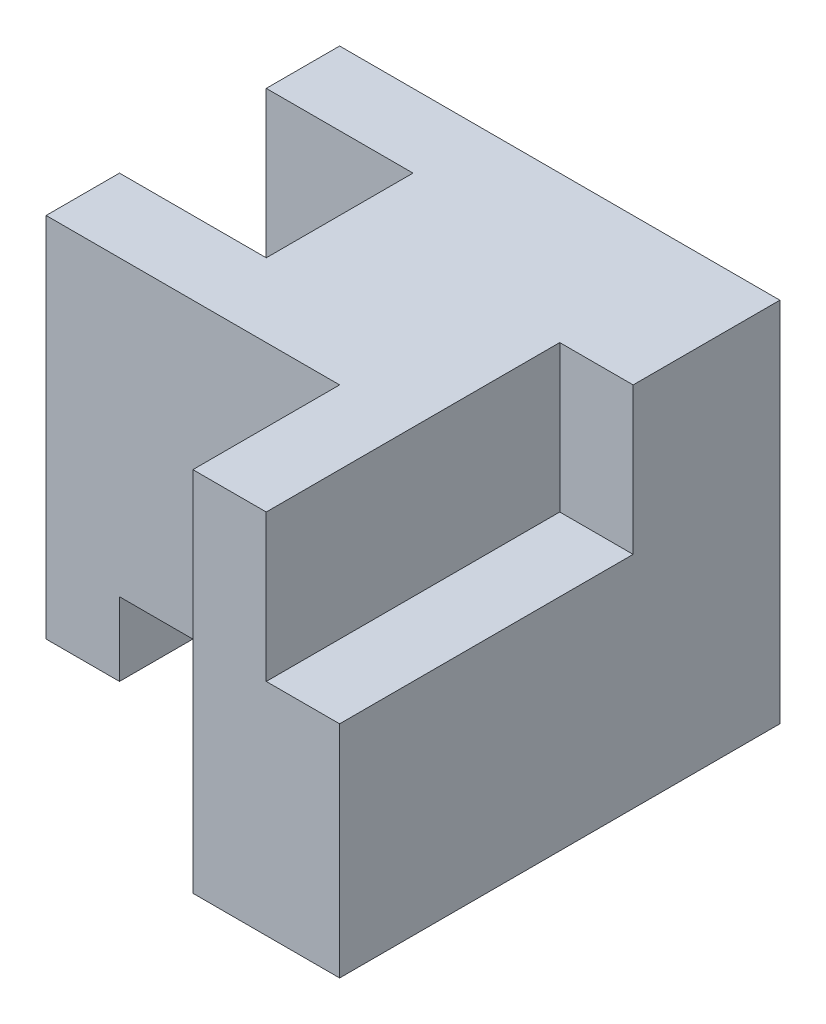
SolidWorks part; units mm, degrees
ref_plane "Front Plane" through (0, 0, 0) normal (0, 0, 1) x (1, 0, 0)
ref_plane "Top Plane" through (0, 0, 0) normal (0, 1, 0) x (1, 0, 0)
ref_plane "Right Plane" through (0, 0, 0) normal (1, 0, 0) x (0, 0, -1)
sketch "Sketch1" plane through (0, 0, 0) normal (0, 0, 1) x (1, 0, 0)
  line L0 (120, 20) -> (80, 20)
  line L1 (120, 100) -> (-120, 100)
  line L2 (120, 100) -> (120, -100)
  line L3 (120, -100) -> (-120, -100)
  line L4 (-120, 100) -> (-120, -100)
  line L5 (120, 100) -> (-120, -100) construction
  line L6 (120, -100) -> (-120, 100) construction
  line L7 (80, 20) -> (80, 100)
  line L8 (80, 100) -> (40, 100)
  line L9 (40, 100) -> (40, -100)
  line L10 (-120, -100) -> (-80, -100)
  line L11 (-80, -100) -> (-80, -60)
  line L12 (-80, -60) -> (40, -60)
  point P0 (0, 0)
  dimension "D1" = 200
  dimension "D2" = 240
extrude "Boss-Extrude1" add sketch "Sketch1" along normal blind 120 contours L1 L9 L3 L2 L0 L7 region at (75, -15, 0)
extrude "Boss-Extrude2" add sketch "Sketch1<3>" against normal blind 120 contours L1 L9 L3 L2 L0 L7 region at (75, -15, 0)
sketch "Sketch1<3>" plane through (0, 0, 0) normal (0, 0, 1) x (1, 0, 0) same geometry as "Sketch1"
sketch "Sketch3" plane through (80, 0, 0) normal (1, 0, 0) x (0, 0, -1)
  line L0 (40, 100) -> (40, 20)
  line L1 (-120, 100) -> (120, 100) construction
  line L2 (-120, 20) -> (120, 20) construction
  line L3 (40, 100) -> (120, 100)
  line L4 (120, 100) -> (120, 20)
  line L5 (120, 20) -> (40, 20)
extrude "Boss-Extrude3" add sketch "Sketch3" along normal blind 40
extrude "Boss-Extrude4" add sketch "Sketch1<4>" along normal blind 40 contours L11 L12 L9 L1 L4 L3 region at (-43.5294, 14.1176, 0)
sketch "Sketch1<4>" plane through (0, 0, 0) normal (0, 0, 1) x (1, 0, 0) same geometry as "Sketch1"
extrude "Boss-Extrude5" add sketch "Sketch1<5>" against normal blind 120 contours L11 L12 L9 L1 L4 L3 region at (-43.5294, 14.1176, 0)
sketch "Sketch1<5>" plane through (0, 0, 0) normal (0, 0, 1) x (1, 0, 0) same geometry as "Sketch1"
sketch "Sketch8" plane through (0, 100, 0) normal (0, 1, 0) x (1, 0, 0)
  line L0 (-120, 0) -> (120, 0)
  line L1 (-120, -40) -> (-120, 120) construction
  line L3 (-120, 80) -> (120, 80)
  line L4 (120, 120) -> (120, 40) construction
  line L5 (120, -120) -> (120, 40) construction
split "Split4" trim tools "Sketch8" bodies to split 105 resulting bodies 113 114 115
chamfer "Chamfer4" distance 80 angle 45 1 edges at (-120, 100, -40)
combine bodies "Combine2" operation type add bodies to combine 113 115 114
